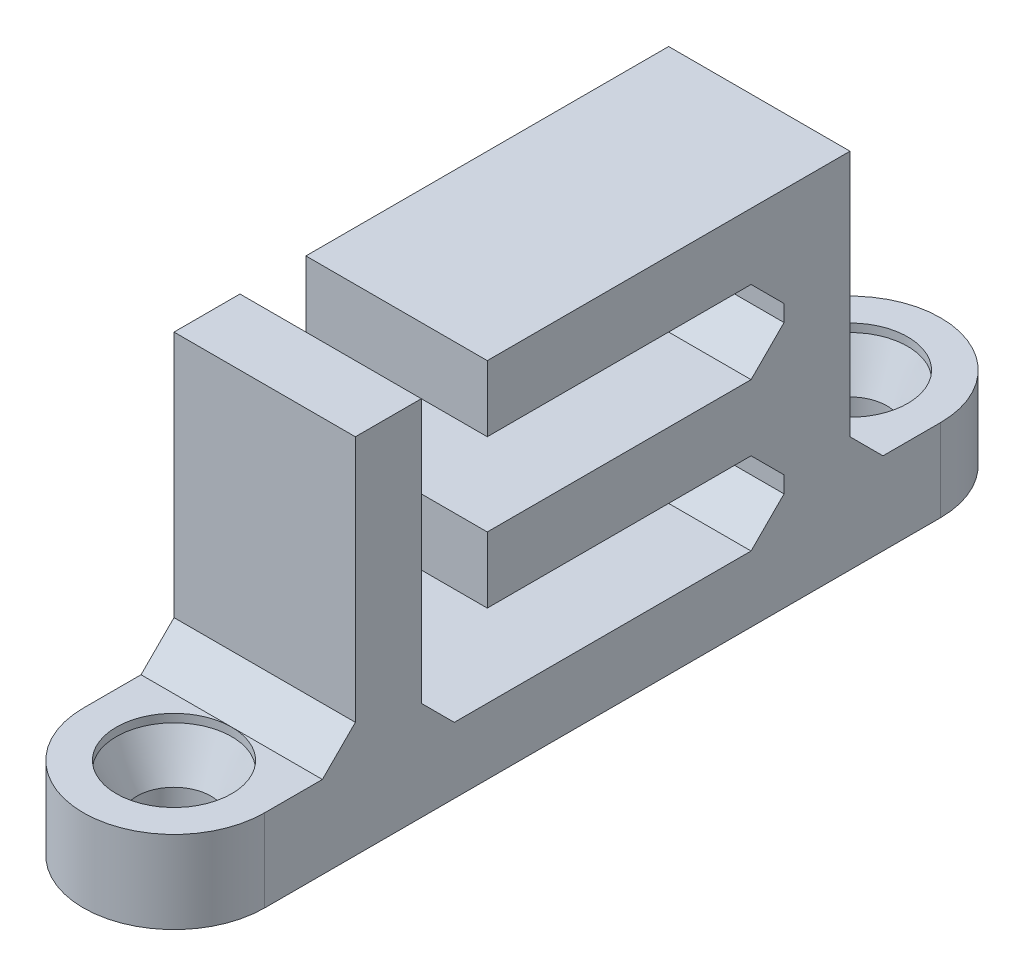
SolidWorks part; units mm, degrees
ref_plane "Front" through (0, 0, 0) normal (0, 0, 1) x (1, 0, 0)
ref_plane "Top" through (0, 0, 0) normal (0, 1, 0) x (1, 0, 0)
ref_plane "Right" through (0, 0, 0) normal (1, 0, 0) x (0, 0, -1)
sketch "Sketch1" plane through (0, 0, 0) normal (1, 0, 0) x (0, 0, -1)
  line L0 (0, 0) -> (0, 54)
  line L5 (0, 0) -> (30, 0)
  line L6 (30, 0) -> (30, 9)
  line L7 (30, 9) -> (26, 9)
  line L8 (0, 54) -> (4, 54)
  line L9 (4, 54) -> (4, 22)
  line L10 (4, 4) -> (26, 4)
  line L11 (26, 4) -> (26, 9)
  line L12 (4, 9) -> (30, 9)
  line L13 (30, 9) -> (30, 18)
  line L14 (30, 18) -> (26, 18)
  line L15 (26, 18) -> (26, 13)
  line L16 (26, 13) -> (4, 13)
  line L17 (4, 18) -> (30, 18)
  line L18 (30, 18) -> (30, 27)
  line L19 (30, 27) -> (26, 27)
  line L20 (26, 27) -> (26, 22)
  line L21 (26, 22) -> (4, 22)
  line L22 (4, 18) -> (4, 13)
  line L23 (4, 9) -> (4, 4)
  line L24 (4, 27) -> (30, 27)
  line L25 (30, 27) -> (30, 36)
  line L26 (30, 36) -> (26, 36)
  line L27 (26, 36) -> (26, 31)
  line L28 (26, 31) -> (4, 31)
  line L29 (4, 36) -> (30, 36)
  line L30 (30, 36) -> (30, 45)
  line L31 (30, 45) -> (26, 45)
  line L32 (26, 45) -> (26, 40)
  line L33 (26, 40) -> (4, 40)
  line L34 (4, 45) -> (30, 45)
  line L35 (30, 45) -> (30, 54)
  line L36 (30, 54) -> (26, 54)
  line L37 (26, 54) -> (26, 49)
  line L38 (26, 49) -> (4, 49)
  line L39 (26, 9) -> (26, 49)
  line L40 (30, 54) -> (30, 9)
  line L41 (4, 54) -> (26, 54)
  line L42 (30, 54) -> (30, 58)
  line L43 (30, 58) -> (0, 58)
  line L44 (0, 58) -> (0, 54)
  dimension "D2" = 4
  dimension "D3" = 4
  dimension "D4" = 4
  dimension "D5" = 4
  dimension "D6" = 4
  dimension "D7" = 5
  dimension "D8" = 5
  dimension "D11" = 5
  dimension "D12" = 30
  dimension "D13" = 4
  dimension "D14" = 4
  dimension "D15" = 5
  dimension "D16" = 5
  dimension "D19" = 5
  dimension "D21" = 4
  dimension "D22" = 4
extrude "Boss-Extrude1" add sketch "Sketch1" along normal blind 11 contours L32 L33 L9 L29 L30 L31 | L23 L12 L13 L14 L15 L16 L22 L17 L18 L19 L20 L21 L9 L8 L0 L5 L6 L7 L11 L10 | L27 L28 L9 L24 L25 L26 | L37 L38 L9 L34 L35 L36 | L43 L44 L8 L41 L36 L42 | L39 L31 L35 L36 L37 | L39 L26 L30 L31 L32 | L39 L19 L25 L26 L27 | L39 L14 L18 L19 L20 | L39 L7 L13 L14 L15 region at (0, 27, -0.6177) region at (0, 56, -15) region at (0, 13.5, -28) region at (0, 47, -15) region at (0, 49.5, -28) region at (0, 22.5, -28) region at (0, 31.5, -28) region at (0, 38, -15) region at (0, 40.5, -28) region at (0, 29, -15)
sketch "Sketch2" plane through (0, 58, 0) normal (0, 1, 0) x (1, 0, 0)
  line L0 (11, 30) -> (11, 0) construction
  line L1 (0, 4) -> (11, 4)
  line L2 (0, 4) -> (0, 8)
  line L3 (0, 8) -> (11, 8)
  line L4 (11, 4) -> (11, 8)
  dimension "D1" = 4
extrude "Cut-Extrude2" cut sketch "Sketch2" against normal up to vertex (54 mm away) up to point (11, 4, -4)
sketch "Sketch3" plane through (0, 0, 0) normal (0, 1, 0) x (1, 0, 0)
  line L0 (5.5, 0.133) -> (5.5, -2.7099) construction
  line L2 (0, 0) -> (0, -5.5)
  line L4 (11, 0) -> (11, -5.5)
  line L5 (11, 0) -> (0, 0) construction
  line L6 (0, 0) -> (11, 0)
  line L7 (11, 35.5) -> (11, 30)
  line L8 (11, 30) -> (0, 30)
  line L9 (0, 30) -> (0, 35.5)
  arc A0 (0, -5.5) -> (11, -5.5) centre (5.5, -5.5) ccw
  circle A1 centre (5.5, -5.5) radius 2.25
  arc A2 (11, 35.5) -> (0, 35.5) centre (5.5, 35.5) ccw
  circle A3 centre (5.5, 35.5) radius 2.25
  point P3 (5.5, -1.2884)
  dimension "D1" = 4.5
  dimension "D2" = 4.5
extrude "Boss-Extrude2" add sketch "Sketch3" along normal blind 5
sketch "Sketch4" plane through (0, 5, 0) normal (0, 1, 0) x (1, 0, 0)
  circle A0 centre (5.5, -5.5) radius 3.5
  circle A1 centre (5.5, 35.5) radius 3.5
  dimension "D1" = 7
  dimension "D2" = 7
extrude "Cut-Extrude3" cut sketch "Sketch4" against normal blind 3
chamfer "Chamfer1" distance 2.5 distance2 1.25 2 edges at (5.5, 2, -32) (5.5, 2, 9) first distance on face at (5.5, 2, -32) first distance on face at (5.5, 2, 9)
chamfer "Chamfer2" distance 2 angle 45 15 edges at (5.5, 9, -26) (5.5, 18, -26) (5.5, 27, -26) (5.5, 36, -26) (5.5, 45, -26) (5.5, 54, -26) (5.5, 49, -26) (5.5, 40, -26) (5.5, 31, -26) (5.5, 22, -26) (5.5, 13, -26) (5.5, 4, -26) (5.5, 4, -4) (5.5, 5, 0) (5.5, 5, -30)
sketch "Sketch5" plane through (11, 0, 0) normal (1, 0, 0) x (0, 0, -1)
  line L0 (24, 31) -> (8, 31) construction
  line L1 (-10.7785, 65.4835) -> (39.6851, 65.4835)
  line L2 (-10.7785, 65.4835) -> (-10.7785, 31)
  line L3 (-10.7785, 31) -> (39.6851, 31)
  line L4 (39.6851, 65.4835) -> (39.6851, 31)
extrude "Cut-Extrude4" [suppressed] cut sketch "Sketch5" against normal through all
sketch "Sketch6" plane through (0, 0, 0) normal (-1, 0, 0) x (0, 0, 1)
  line L0 (-24, 22) -> (-8, 22) construction
  line L1 (-33.9659, 58) -> (5.0593, 58)
  line L2 (-33.9659, 58) -> (-33.9659, 22)
  line L3 (-33.9659, 22) -> (5.0593, 22)
  line L4 (5.0593, 58) -> (5.0593, 22)
  line L5 (-30, 58) -> (-8, 58) construction
extrude "Cut-Extrude5" cut sketch "Sketch6" against normal through all
sketch "Sketch7" [suppressed] plane through (0, 0, 0) normal (-1, 0, 0) x (0, 0, 1)
  line L0 (-24, 40) -> (-8, 40) construction
  line L1 (-37.5825, 58) -> (8.4235, 58)
  line L2 (-37.5825, 58) -> (-37.5825, 40)
  line L3 (-37.5825, 40) -> (8.4235, 40)
  line L4 (8.4235, 58) -> (8.4235, 40)
  line L5 (-30, 58) -> (-8, 58) construction
extrude "Cut-Extrude6" [suppressed] cut sketch "Sketch7" against normal through all
